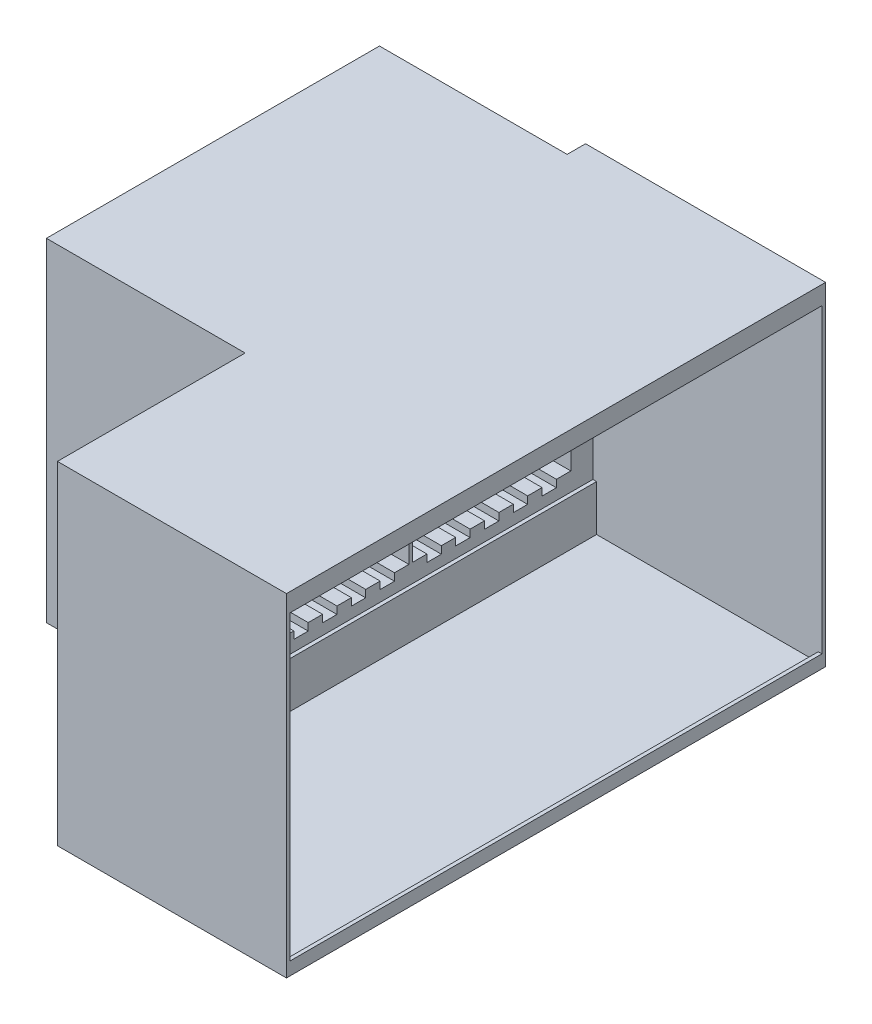
SolidWorks part; units mm, degrees
other "Исправление1"
sketch "Эскиз13" plane through (1050, -360, 1224.5) normal (0.916, -0.3443, 0.206) x (0.3981, 0.8438, -0.36)
ref_plane "Спереди" through (0, 0, 0) normal (0, 0, 1) x (1, 0, 0)
ref_plane "Сверху" through (0, 0, 0) normal (0, 1, 0) x (1, 0, 0)
ref_plane "Справа" through (0, 0, 0) normal (1, 0, 0) x (0, 0, -1)
other "Configuration Table"
sketch "Основа эскиз" plane through (0, 0, 0) normal (1, 0, 0) x (0, 0, -1)
  line L1 (-477.5, 452.3) -> (477.5, 452.3)
  line L2 (-477.5, 452.3) -> (-477.5, -452.3)
  line L3 (-477.5, -452.3) -> (477.5, -452.3)
  line L4 (477.5, 452.3) -> (477.5, -452.3)
  point P4 (0, 452.3)
  point P8 (-477.5, 0)
  dimension "D2" = 955
  dimension "D1" = 904.6
extrude "Основа" add sketch "Основа эскиз" along normal blind 1162.3
sketch "Вырез коретки эскиз" plane through (1162.3, 0, 0) normal (1, 0, 0) x (0, 0, -1)
  line L5 (477.5, 452.3) -> (-477.5, 452.3) construction
  line L6 (-477.5, 402.3) -> (467.5, 402.3)
  line L7 (-477.5, -452.3) -> (477.5, -452.3) construction
  line L8 (-477.5, 402.3) -> (-477.5, -317.7)
  line L9 (-477.5, -317.7) -> (467.5, -317.7)
  line L10 (467.5, 402.3) -> (467.5, -317.7)
  line L11 (-477.5, 452.3) -> (-477.5, -452.3) construction
  line L12 (477.5, -452.3) -> (477.5, 452.3) construction
  point P0 (0, 0)
  dimension "D3" = 10
  dimension "D4" = 134.6
extrude "Вырез коретки" cut sketch "Вырез коретки эскиз" against normal blind 622.3
sketch "вырез ячейки эскиз" plane through (540, 0, 0) normal (1, 0, 0) x (0, 0, -1)
  line L0 (467.5, 402.3) -> (-477.5, 402.3) construction
  line L1 (-462.5, 402.3) -> (-32.5, 402.3)
  line L2 (-462.5, 402.3) -> (-462.5, 82.3)
  line L3 (-462.5, 82.3) -> (-32.5, 82.3)
  line L4 (-32.5, 402.3) -> (-32.5, 82.3)
  line L17 (-477.5, 402.3) -> (-477.5, -317.7) construction
  dimension "D7" = 430
  dimension "D8" = 320
  dimension "D1" = 15
extrude "вырез ячейки" cut sketch "вырез ячейки эскиз" against normal blind 510
sketch "вырез двери эскиз" plane through (0, 0, 0) normal (-1, 0, 0) x (0, 0, 1)
  line L1 (32.5, 402.3) -> (467.5, 402.3)
  line L2 (32.5, 402.3) -> (32.5, 82.3)
  line L3 (32.5, 82.3) -> (467.5, 82.3)
  line L4 (467.5, 402.3) -> (467.5, 82.3)
  line L6 (462.5, 82.3) -> (32.5, 82.3) construction
  line L7 (32.5, 82.3) -> (32.5, 402.3) construction
  line L8 (462.5, 402.3) -> (462.5, 82.3) construction
  line L9 (462.5, 402.3) -> (462.5, 82.3) construction
  line L10 (32.5, 402.3) -> (462.5, 402.3) construction
  dimension "D2" = 5
extrude "вырез двери" cut sketch "вырез двери эскиз" against normal blind 10
sketch "Вырез основание низ эскиз" plane through (0, -317.7, 0) normal (0, 1, 0) x (1, 0, 0)
  line L0 (1162.3, -477.5) -> (1162.3, 467.5) construction
  line L1 (550, 467.5) -> (1152.3, 467.5)
  line L2 (550, 467.5) -> (550, -477.5)
  line L3 (550, -477.5) -> (1152.3, -477.5)
  line L4 (1152.3, 467.5) -> (1152.3, -477.5)
  line L5 (540, 467.5) -> (1162.3, 467.5) construction
  line L6 (540, -477.5) -> (1162.3, -477.5) construction
  dimension "D1" = 10
  dimension "D2" = 602.3
extrude "Вырез основание низ" cut sketch "Вырез основание низ эскиз" against normal blind 124.6
sketch "Вырез основания верх эскиз" plane through (0, 402.3, 0) normal (0, -1, 0) x (1, 0, 0)
  line L0 (540, 477.5) -> (1162.3, 477.5) construction
  line L1 (550, -467.5) -> (1152.3, -467.5)
  line L2 (550, -467.5) -> (550, 477.5)
  line L3 (550, 477.5) -> (1152.3, 477.5)
  line L4 (1152.3, -467.5) -> (1152.3, 477.5)
  line L5 (540, -467.5) -> (1162.3, -467.5) construction
  line L6 (1162.3, -467.5) -> (1162.3, 477.5) construction
  dimension "D1" = 10
  dimension "D2" = 602.3
extrude "Вырез основание верх" cut sketch "Вырез основания верх эскиз" against normal offset from surface (40 mm away) 10 up to face at (581.15, 452.3, 0)
sketch "вырез полозья эскиз" plane through (540, 0, 0) normal (1, 0, 0) x (0, 0, -1)
  line L0 (-462.5, 82.3) -> (-32.5, 82.3) construction
  line L1 (-423.4091, 82.3) -> (-384.3182, 82.3)
  line L2 (-423.4091, 82.3) -> (-423.4091, 62.3)
  line L3 (-423.4091, 62.3) -> (-384.3182, 62.3)
  line L4 (-384.3182, 82.3) -> (-384.3182, 62.3)
  dimension "D2" = 39.0909
  dimension "D3" = 39.0909
extrude "Вырез полозья" cut sketch "вырез полозья эскиз" against normal blind 510
pattern_linear "Линейный массив полозьев" count 5 spacing 78.1818 along (0, 0, -1) of "Вырез полозья"
pattern_linear "Линейный массив ячеек" count 2 spacing 440 along (0, 0, -1) count 2 spacing 350 along (0, -1, 0) of "Линейный массив полозьев", "вырез двери", "вырез ячейки"
sketch "Основание эскиз" plane through (0, 0, 477.5) normal (0, 0, 1) x (1, 0, 0)
  line L0 (1162.3, -452.3) -> (1162.3, -317.7)
  line L1 (1162.3, -317.7) -> (1152.3, -317.7)
  line L2 (1152.3, -317.7) -> (1152.3, -442.3)
  line L3 (1152.3, -442.3) -> (550, -442.3)
  line L4 (550, -442.3) -> (550, -317.7)
  line L5 (550, -317.7) -> (540, -317.7)
  line L6 (540, -317.7) -> (540, -452.3)
  line L7 (1162.3, -452.3) -> (0, -452.3) construction
  line L8 (540, -452.3) -> (1162.3, -452.3)
  line L9 (1152.3, 402.3) -> (1162.3, 402.3)
  line L10 (1162.3, 402.3) -> (1162.3, 452.3)
  line L11 (1162.3, 452.3) -> (540, 452.3)
  line L12 (1162.3, 452.3) -> (0, 452.3) construction
  line L13 (540, 452.3) -> (540, 402.3)
  line L14 (540, 402.3) -> (550, 402.3)
  line L15 (550, 402.3) -> (550, 442.3)
  line L16 (550, 442.3) -> (1152.3, 442.3)
  line L17 (1152.3, 442.3) -> (1152.3, 402.3)
extrude "Основание" add sketch "Основание эскиз" along normal blind 500
sketch "Стенка боквая эскиз" plane through (0, 0, 977.5) normal (0, 0, 1) x (1, 0, 0)
  line L1 (1162.3, 452.3) -> (540, 452.3)
  line L2 (1162.3, 452.3) -> (1162.3, -452.3)
  line L3 (1162.3, -452.3) -> (540, -452.3)
  line L4 (540, 452.3) -> (540, -452.3)
extrude "Стенка боковая" add sketch "Стенка боквая эскиз" along normal blind 10
sketch "Эскиз14" plane through (0, 0, -477.5) normal (0, 0, -1) x (-1, 0, 0)
  line L0 (-1162.3, 452.3) -> (0, 452.3) construction
  line L1 (0, -452.3) -> (-510, -452.3)
  line L2 (0, -452.3) -> (0, 452.3)
  line L3 (0, 452.3) -> (-510, 452.3)
  line L4 (-510, -452.3) -> (-510, 452.3)
  dimension "D1" = 510
extrude "Вырез-Вытянуть1" cut sketch "Эскиз14" against normal blind 50
sketch "Эскиз15" plane through (1162.3, 0, 0) normal (1, 0, 0) x (0, 0, -1)
  line L1 (-977.5, -317.7) -> (467.5, -317.7)
  line L2 (-977.5, -317.7) -> (-977.5, -442.3)
  line L3 (-977.5, -442.3) -> (467.5, -442.3)
  line L4 (467.5, -317.7) -> (467.5, -442.3)
extrude "Вырез-Вытянуть2" cut sketch "Эскиз15" against normal up to next
sketch "Эскиз16" plane through (1162.3, 0, 0) normal (1, 0, 0) x (0, 0, -1)
  line L0 (467.5, -417.05) -> (467.5, -442.3)
  line L2 (-977.5, -442.3) -> (467.5, -442.3)
  line L3 (-977.5, -442.3) -> (-977.5, -417.05)
  line L4 (-977.5, -417.05) -> (467.5, -417.05)
  line L7 (467.5, -442.3) -> (467.5, 402.3) construction
  point P0 (467.5, -412.2998)
  dimension "D1" = 25.25
extrude "Бобышка-Вытянуть1" add sketch "Эскиз16" against normal blind 10
equation "\"Ширина груза\"= 420"
equation "\"Глубина груза\"= 490"
equation "\"Высота груза\"= 297"
equation "\"Ширина ячейки\"= \"Ширина груза\" + 10"
equation "\"Глубина ячейки\"= \"Глубина груза\" + 10"
equation "\"Высота ячейки\"= \"Высота груза\" + 10 + 13"
equation "\"Колво ячеек ширина\"= 2"
equation "\"Колво ячеек высота\"= 2"
equation "\"Толщина стенки\"= 10"
equation "\"D2@Основа эскиз\"=( \"Ширина ячейки\" + \"Толщина стенки\" + \"Крепление дверцы\" ) * \"Колво ячеек ширина\" + \"Ширина пластины\"+\"Толщина стенки\"*1.5"
equation "\"D1@Основа эскиз\"=( \"Высота ячейки\" + \"Толщина стенки\" + \"Высота пола\" ) * \"Колво ячеек высота\" + \"Толщина стенки\" * 6 + \"Мотор X ширина корпуса\" + \"Мотор Y ширина корпуса\"+40+20"
equation "\"Крепление дверцы\"= 5"
equation "\"D7@вырез ячейки эскиз\"= \"Ширина ячейки\""
equation "\"D1@вырез ячейки эскиз\" = \"Толщина стенки\" + \"Крепление дверцы\""
equation "\"D8@вырез ячейки эскиз\"= \"Высота ячейки\""
equation "\"D2@вырез двери эскиз\"= \"Крепление дверцы\""
equation "\"D1@Основа\"=\"Глубина ячейки\" + \"Глубина каретки\" + \"Толщина стенки\" * 6 + \"Ширина рейки\""
equation "\"D1@Вырез коретки\"=\"Глубина каретки\" + \"Толщина стенки\" * 2 + \"Ширина рейки\""
equation "\"D1@Вырез основание низ эскиз\"=\"Толщина стенки\" "
equation "\"Ширина рейки\"= \"Толщина шестерни\""
equation "\"D1@вырез ячейки\"= \"Глубина ячейки\" + \"Толщина стенки\""
equation "\"D1@вырез двери\"= \"Толщина стенки\""
equation "\"D2@Вырез основание низ эскиз\"=\"Глубина каретки\" + \"Ширина рейки\""
equation "\"Высота рейки\"= 20"
equation "\"D1@Вырез основания верх эскиз\"=\"Толщина стенки\""
equation "\"D2@Вырез основания верх эскиз\"=\"Глубина каретки\" + \"Ширина рейки\" "
equation "\"D1@Вырез основание верх\"=\"Толщина стенки\""
equation "\"D4@Вырез коретки эскиз\"=\"Толщина стенки\"  + \"Высота рейки\" + \"Отступ рейки\" + \"Мотор X ширина корпуса\" + \"Мотор Y ширина корпуса\""
equation "\"D1@Вырез коретки эскиз\"=\"Толщина стенки\"*2+30"
equation "\"D3@Вырез коретки эскиз\" = \"Толщина стенки\""
equation "\"D1@Вырез основание низ\"=\"Мотор X ширина корпуса\" + \"Мотор Y ширина корпуса\"+\"Высота рейки\" + \"Отступ рейки\""
equation "\"Высота пола\"= 20"
equation "\"Колво полозьев\"= 5"
equation "\"D1@вырез полозья эскиз\" = \"Высота пола\""
equation "\"D2@вырез полозья эскиз\" = \"Ширина ячейки\" /  ( \"Колво полозьев\" * 2 + 1 ) "
equation "\"D3@вырез полозья эскиз\"= \"Ширина ячейки\" / ( \"Колво полозьев\" * 2 + 1 )"
equation "\"D1@Вырез полозья\" = \"Глубина ячейки\" + \"Толщина стенки\""
equation "\"D1@Линейный массив полозьев\" = \"Колво полозьев\""
equation "\"D3@Линейный массив полозьев\" = \"Ширина ячейки\" /  ( \"Колво полозьев\" * 2 + 1 )  * 2"
equation "\"D1@Линейный массив ячеек\" = \"Колво ячеек ширина\""
equation "\"D2@Линейный массив ячеек\" = \"Колво ячеек высота\""
equation "\"D3@Линейный массив ячеек\" = \"Ширина ячейки\" + \"Толщина стенки\""
equation "\"D4@Линейный массив ячеек\" = \"Высота ячейки\" + \"Высота пола\" + \"Толщина стенки\""
equation "\"Отступ рейки\"= 20"
equation "\"Глубина каретки\"= \"Глубина ячейки\" + 30 + \"Мотор Y высота корпуса\" + 20"
equation "\"D1@Стенка боковая\" = \"Толщина стенки\""
equation "\"Длинна рейки\"= ( \"Ширина ячейки\" + \"Толщина стенки\" + \"Крепление дверцы\" ) * \"Колво ячеек ширина\" + \"Ширина ячейки выгрузки\" * \"Колво выгрузки\" + \"Толщина стенки\""
equation "\"D1@Основание\" = \"Длинна рейки\" -  ( \"Ширина ячейки\" + \"Толщина стенки\" + \"Крепление дверцы\" )  * \"Колво ячеек ширина\" - \"Толщина стенки\""
equation "\"Отступ шпильки\"= 20"
equation "\"Диаметр шпильки\"= 5"
equation "\"Длинна шпильки\"= ( \"Высота ячейки\" + \"Толщина стенки\" + \"Высота пола\" ) * \"Колво ячеек высота\" + ( \"Толщина стенки\" + \"Отступ рейки\" ) * 2 "
equation "\"Ширина пластины\"= 50  "
equation "\"Высота зона выгрузки\"= \"Высота ячейки\" * 2 + \"Толщина стенки\" * 2"
equation "\"Колво выгрузки\"= 1"
equation "\"D1@Эскиз14\"= \"Толщина стенки\" + \"Глубина ячейки\""
equation "\"D1@Вырез-Вытянуть1\"= \"Ширина пластины\""
equation "\"Ширина ячейки выгрузки\"= \"Ширина ячейки\" + \"Толщина стенки\" + \"Отступ крепления мотора фиксации\"*2"
equation "\"Отступ крепления мотора фиксации\" = 30"
equation "\"Мотор X ширина корпуса\"= 42.3"
equation "\"Мотор X высота корпуса\"= 42.3"
equation "\"Мотор X длина корпуса\"= 40"
equation "\"Мотор X вылет вала\"= 19.8"
equation "\"Мотор Y ширина корпуса\"= 42.3"
equation "\"Мотор Y высота корпуса\"= 42.3"
equation "\"Мотор Y длина корпуса\"= 48"
equation "\"Мотор Y вылет вала\"= 30"
equation "\"Мотор Z ширина корпуса\"= 42"
equation "\"Мотор Z высота корпуса\"= 42"
equation "\"Мотор Z длина корпуса\"= 40"
equation "\"Мотор Z вылет вала\"= 23"
equation "\"Мотор диаметр вала ПРЕДВ\"= 5"
equation "\"Мотор шаг крепления ПРЕДВ\"= 31"
equation "\"Мотор диаметр отверстий ПРЕДВ\"= 3"
equation "\"Мотор глубина отверстий ПРЕДВ\"= 4.5"
equation "\"Мотор диаметр буртика ПРЕДВ\"= 22"
equation "\"Мотор высота буртика ПРЕДВ\"= 2"
equation "\"Мотор диаметр шкива ПРЕДВ\"= 16"
equation "\"Мотор длина шкива ПРЕДВ\"= 12"
equation "\"Мотор отступ шкива ПРЕДВ\"= 5"
equation "\"Мотор X шаг градусов\"= 1.8"
equation "\"Мотор Y шаг градусов\"= 1.8"
equation "\"Мотор Z шаг градусов\"= 1.8"
equation "\"Мотор Y диаметр ротора\"= 25.78"
equation "\"Толщина шестерни\"= 10"
equation "\"D1@Бобышка-Вытянуть1\"=\"Толщина стенки\""
